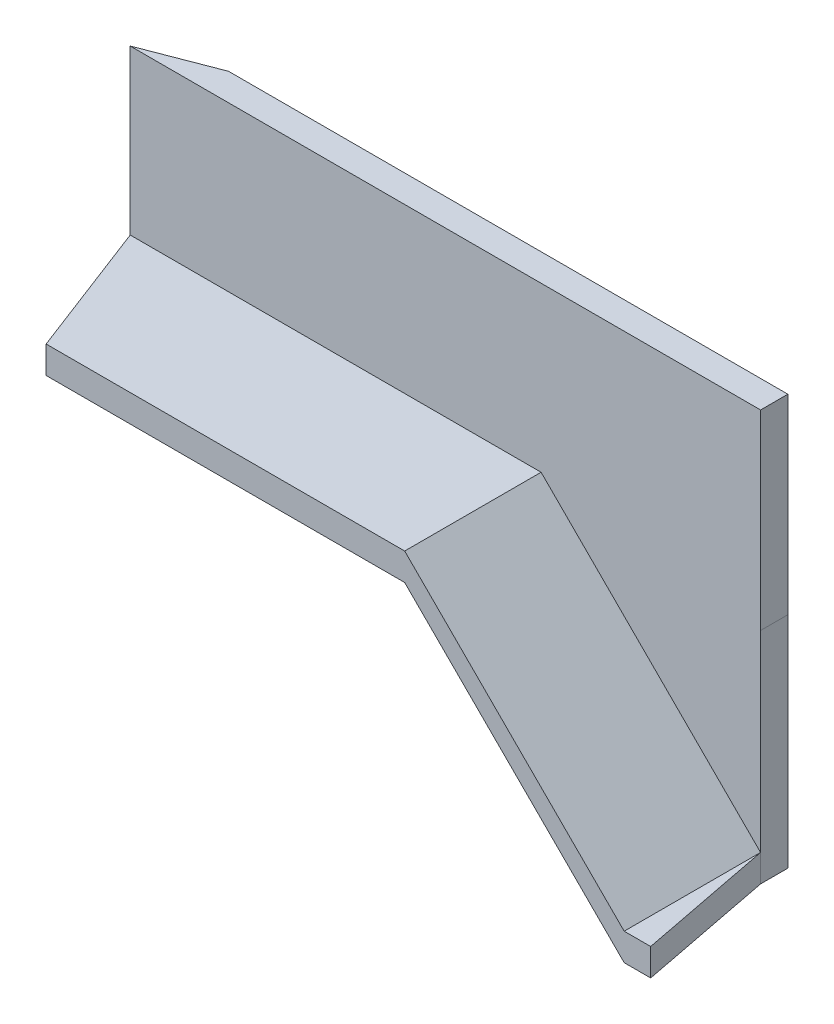
SolidWorks part; units mm, degrees
ref_plane "Płaszczyzna przednia" through (0, 0, 0) normal (0, 0, 1) x (1, 0, 0)
ref_plane "Płaszczyzna górna" through (0, 0, 0) normal (0, 1, 0) x (1, 0, 0)
ref_plane "Płaszczyzna prawa" through (0, 0, 0) normal (1, 0, 0) x (0, 0, -1)
sketch "Sketch1" plane through (0, 0, 0) normal (0, 0, 1) x (1, 0, 0)
  line L1 (-46.1789, 6.3455) -> (22.8211, 6.3455)
  line L2 (-46.1789, 6.3455) -> (-46.1789, -7.6545)
  line L3 (-46.1789, -7.6545) -> (22.8211, -7.6545)
  line L4 (22.8211, 6.3455) -> (22.8211, -7.6545)
  dimension "D1" = 14
  dimension "D2" = 69
extrude "Boss-Extrude1" add sketch "Sketch1" along normal blind 2
sketch "Sketch2" plane through (0, 0, 2) normal (0, 0, 1) x (1, 0, 0)
  line L1 (-46.1789, 6.3455) -> (6.7317, 6.3455)
  line L2 (-46.1789, 6.3455) -> (-46.1789, 4.3455)
  line L3 (-46.1789, 4.3455) -> (6.7317, 4.3455)
  line L4 (6.7317, 6.3455) -> (6.7317, 4.3455)
extrude "Boss-Extrude2" add sketch "Sketch2" along normal blind 4
sketch "Sketch4" plane through (0, 6.3455, 0) normal (0, 1, 0) x (1, 0, 0)
  line L0 (-18.1789, 0) -> (-33.8094, -6)
  line L4 (-33.8094, -6) -> (-46.1789, -6)
  line L5 (-46.1789, -6) -> (-46.1789, 0)
  line L6 (-46.1789, 0) -> (-18.1789, 0)
  dimension "D1" = 21
  dimension "D2" = 28
extrude "Cut-Extrude1" cut sketch "Sketch4" against normal blind 20 and the other way blind 20
sketch "Sketch5" plane through (0, 6.3455, 0) normal (0, 1, 0) x (1, 0, 0)
  line L1 (-33.8094, -6) -> (-18.1789, 0) construction
  line L7 (-33.8094, -6) -> (-23.3896, -2.0002)
  line L8 (-23.3896, -2.0002) -> (-21.8542, -6)
  line L9 (6.7317, -6) -> (-33.8094, -6) construction
  line L10 (-21.8542, -6) -> (-33.8094, -6)
  dimension "D1" = 90
extrude "Cut-Extrude2" cut sketch "Sketch5" against normal blind 2
sketch "Sketch6" plane through (0, 0, 2) normal (0, 0, 1) x (1, 0, 0)
  line L0 (6.7317, 6.3455) -> (22.8217, 22.4355)
  line L1 (22.8217, 22.4355) -> (22.8211, 6.3455)
  line L2 (22.8211, 6.3455) -> (6.7317, 6.3455)
  dimension "D1" = 45
  dimension "D2" = 16.0895
  dimension "D3" = 16.09
extrude "Boss-Extrude3" add sketch "Sketch6" against normal up to surface (2 mm away) up to face at (2.3211, -0.6545, 0)
sketch "Sketch7" plane through (0, 0, 2) normal (0, 0, 1) x (1, 0, 0)
  line L0 (6.7317, 4.3455) -> (22.8216, 20.4355)
  line L1 (22.8211, 6.3455) -> (22.8217, 22.4355) construction
  line L2 (22.8216, 20.4355) -> (22.8217, 22.4355)
  line L3 (22.8217, 22.4355) -> (6.7317, 6.3455)
  line L4 (6.7317, 6.3455) -> (6.7317, 4.3455)
  dimension "D1" = 2
extrude "Boss-Extrude4" add sketch "Sketch7" along normal up to surface (4 mm away) up to face at (-7.5613, 5.3455, 6)
sketch "Sketch8" plane through (0, 0, 6) normal (0, 0, 1) x (1, 0, 0)
  line L0 (22.8217, 22.4355) -> (6.7317, 6.3455)
  line L1 (6.7317, 6.3455) -> (-21.8542, 6.3455)
  line L2 (-21.8542, 6.3455) -> (-21.8542, 4.3455)
  line L3 (-21.8542, 4.3455) -> (6.7317, 4.3455)
  line L4 (6.7317, 4.3455) -> (22.8216, 20.4355)
  line L5 (22.8216, 20.4355) -> (22.8217, 22.4355)
extrude "Boss-Extrude5" add sketch "Sketch8" along normal blind 6
sketch "Sketch9" plane through (0, 4.3455, 0) normal (0, -1, 0) x (1, 0, 0)
  line L0 (-23.389, 2) -> (-21.8542, 6)
  line L1 (-21.8542, 6) -> (-19.552, 12)
  line L2 (-21.8542, 12) -> (6.7317, 12) construction
  line L3 (-19.552, 12) -> (-21.8542, 12)
  line L4 (-21.8542, 12) -> (-23.389, 2)
extrude "Cut-Extrude3" cut sketch "Sketch9" against normal blind 6
sketch "Sketch10" plane through (0, 4.3455, 0) normal (0, -1, 0) x (1, 0, 0)
  line L0 (22.8216, 12) -> (24.7654, 12)
  line L1 (24.7654, 12) -> (22.8211, 2)
  line L2 (22.8211, 2) -> (22.8216, 12)
  dimension "D1" = 11
extrude "Boss-Extrude6" add sketch "Sketch10" against normal blind 2 from vertex starting at point (22.8216, 20.4355, 2)
mirror "Mirror1" about plane through (-46.1789, -7.6545, 2) normal (0, 1, 0) of bodies 110
sketch "Sketch11" plane through (0, 0, 2) normal (0, 0, 1) x (1, 0, 0)
  line L1 (-27.2649, -7.6545) -> (33.4941, -7.6545)
  line L2 (-27.2649, -7.6545) -> (-27.2649, 24.2209)
  line L3 (-27.2649, 24.2209) -> (33.4941, 24.2209)
  line L4 (33.4941, -7.6545) -> (33.4941, 24.2209)
  point P5 (0, 0)
extrude "Cut-Extrude4" cut sketch "Sketch11" against normal blind 20 and the other way blind 20
